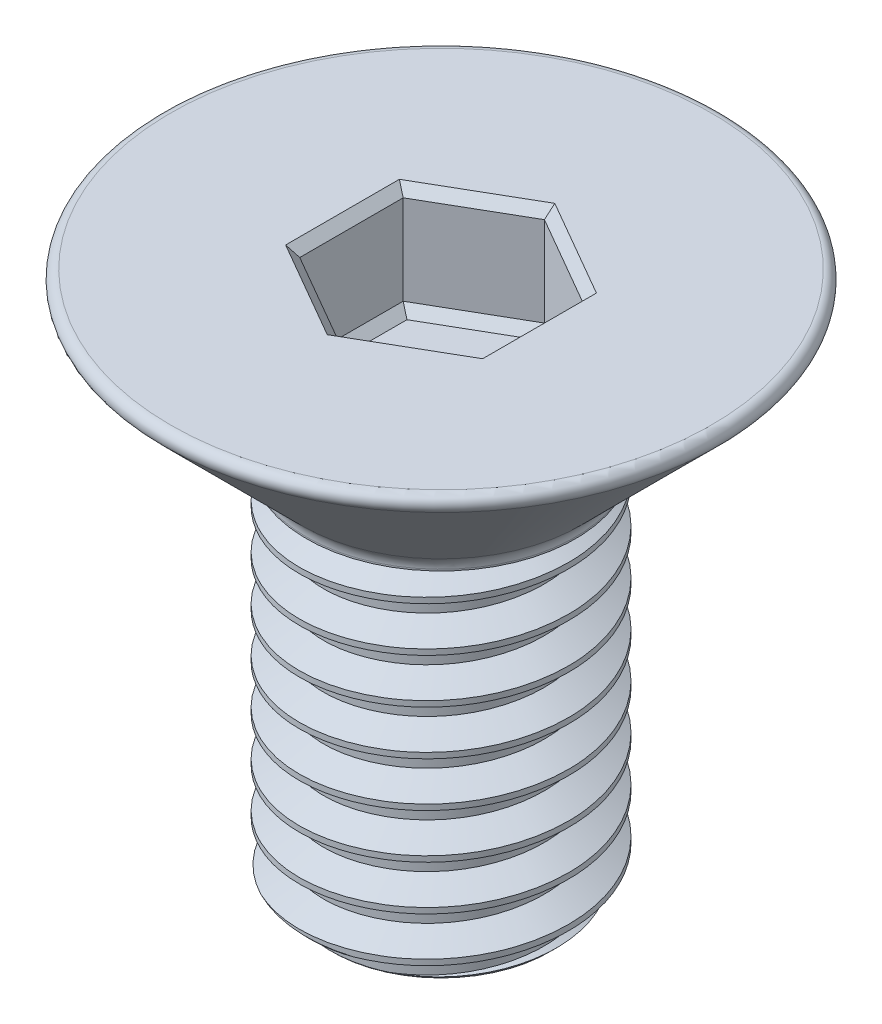
SolidWorks part; units mm, degrees
material "AISI Type A2 Tool Steel"
ref_plane "Front Plane" through (0, 0, 0) normal (0, 0, 1) x (1, 0, 0)
ref_plane "Top Plane" through (0, 0, 0) normal (0, 1, 0) x (1, 0, 0)
ref_plane "Right Plane" through (0, 0, 0) normal (1, 0, 0) x (0, 0, -1)
sketch "Sketch1" plane through (0, 0, 0) normal (0, 1, 0) x (1, 0, 0)
  circle A0 centre (0, 0) radius 1.5
  dimension "D1" = 3
extrude "Boss-Extrude1" add sketch "Sketch1" along normal blind 4.14
thread "Thread1" pitch 0.5 method cut profile "Thread Profile1" start angle 0, offset 1, length 0, pitch 0.5, diameter 3
ref_plane "Plane1" through (-1.5, 5.14, 0) normal (0, 0, 1) x (-1, 0, 0)
sketch "Thread Profile1" plane through (-1.5, 5.14, 0) normal (0, 0, 1) x (-1, 0, 0)
  line L0 (0, 0) -> (0, 0.5) construction
  line L11 (0, 0) -> (0, 0.4375)
  line L12 (0, 0.4375) -> (-0.2706, 0.2812)
  line L13 (-0.2706, 0.2812) -> (-0.2706, 0.1562)
  line L15 (-0.2706, 0.1562) -> (0, 0)
  line L17 (-0.2706, 0.2187) -> (0, 0.2187) construction
  point P2 (0, 0)
  dimension "Pitch" = 0.5
  dimension "Profile_Angle" = 60
  dimension "Profile_Land" = 0.125
  dimension "Profile_Height" = 0.2706
sketch "Sketch5" plane through (0, 4.14, 0) normal (0, 1, 0) x (1, 0, 0)
  circle A0 centre (0, 0) radius 1.5
  dimension "D1" = 3
extrude "Boss-Extrude2" add sketch "Sketch5" along normal blind 0.1
sketch "Sketch6" plane through (0, 4.24, 0) normal (0, 1, 0) x (1, 0, 0)
  circle A0 centre (0, 0) radius 1.5
  dimension "D1" = 3
extrude "Boss-Extrude3" add sketch "Sketch6" along normal blind 1.76 draft 45 draft outward yes
sketch "Sketch7" plane through (0, 0, 0) normal (0, 0, 1) x (1, 0, 0)
  line L0 (0, 0) -> (0, 0.1997) construction
  line L1 (0, 0) -> (1.51, 0) construction
  line L2 (1.51, 0) -> (1.51, 0.3)
  line L3 (1.51, 0.3) -> (1.21, 0)
  line L4 (1.21, 0) -> (1.51, 0)
  dimension "D1" = 45
  dimension "D2" = 0.3
  dimension "D3" = 1.51
revolve "Cut-Revolve1" cut sketch "Sketch7" angle 360 about L0
fillet "Fillet1" radius 0.1 1 edges at (0, 6, 3.26)
fillet "Fillet2" radius 0.2 1 edges at (0, 4.24, 1.5)
sketch "Sketch8" plane through (0, 6, 0) normal (0, 1, 0) x (1, 0, 0)
  line L1 (0, 1.1547) -> (-1, 0.5774)
  line L2 (-1, 0.5774) -> (-1, -0.5774)
  line L3 (-1, -0.5774) -> (0, -1.1547)
  line L4 (0, -1.1547) -> (1, -0.5774)
  line L5 (1, -0.5774) -> (1, 0.5774)
  line L6 (1, 0.5774) -> (0, 1.1547)
  circle A0 centre (0, 0) radius 1 construction
  dimension "D1" = 2
extrude "Cut-Extrude1" cut sketch "Sketch8" against normal blind 1.1
chamfer "Chamfer1" distance 0.1 angle 45 6 edges at (-1, 6, 0) (-0.5, 6, 0.866) (0.5, 6, 0.866) (1, 6, 0) (0.5, 6, -0.866) (-0.5, 6, -0.866)
sketch "Sketch9" plane through (0, 4.9, 0) normal (0, 1, 0) x (1, 0, 0)
  line L1 (0, 1.1547) -> (-1, 0.5774)
  line L2 (-1, 0.5774) -> (-1, -0.5774)
  line L3 (-1, -0.5774) -> (0, -1.1547)
  line L4 (0, -1.1547) -> (1, -0.5774)
  line L5 (1, -0.5774) -> (1, 0.5774)
  line L6 (1, 0.5774) -> (0, 1.1547)
  circle A0 centre (0, 0) radius 1 construction
extrude "Cut-Extrude2" cut sketch "Sketch9" against normal blind 0.1 draft 45
